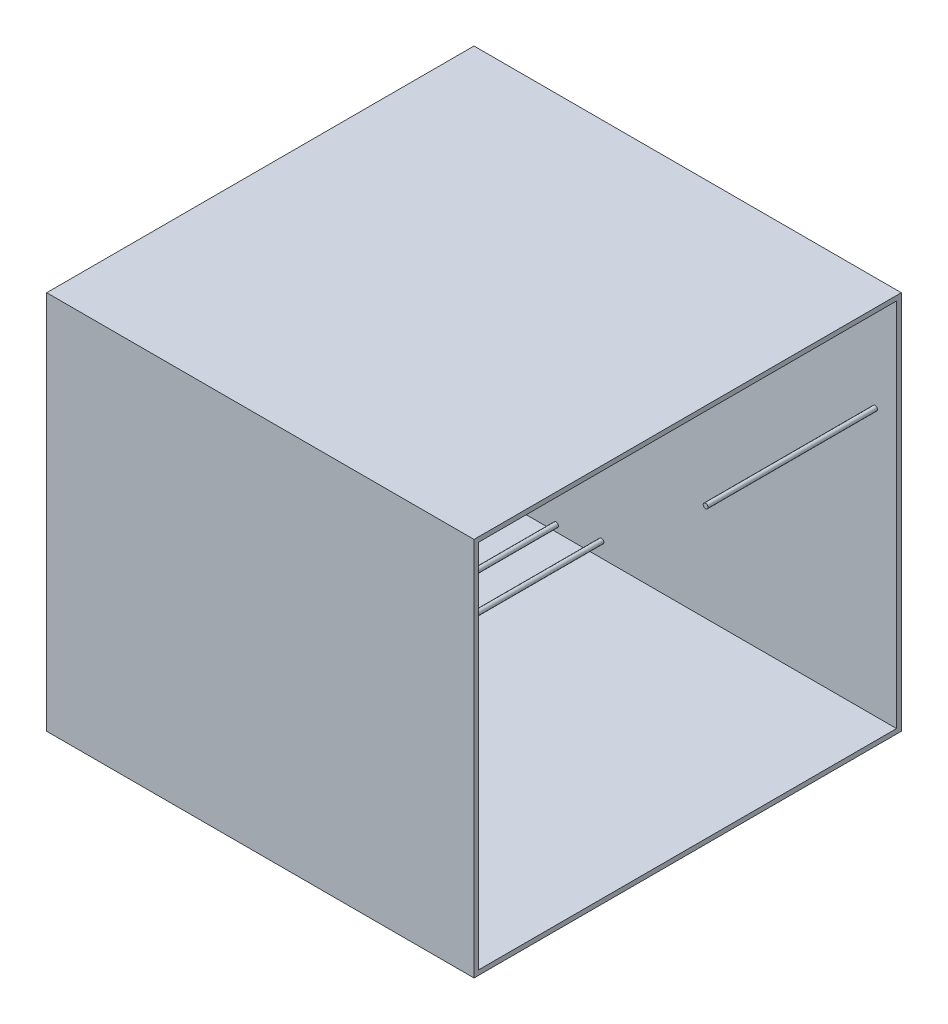
SolidWorks part; units mm, degrees
ref_plane "Plano frontal" through (0, 0, 0) normal (0, 0, 1) x (1, 0, 0)
ref_plane "Plano superior" through (0, 0, 0) normal (0, 1, 0) x (1, 0, 0)
ref_plane "Plano direito" through (0, 0, 0) normal (1, 0, 0) x (0, 0, -1)
sketch "Esboço1" plane through (0, 0, 0) normal (1, 0, 0) x (0, 0, -1)
  line L1 (0, 0) -> (450, 0)
  line L2 (0, 0) -> (0, 400)
  line L3 (0, 400) -> (450, 400)
  line L4 (450, 0) -> (450, 400)
  line L5 (5, 5) -> (445, 5)
  line L6 (5, 5) -> (5, 395)
  line L7 (5, 395) -> (445, 395)
  line L8 (445, 5) -> (445, 395)
  line L9 (5, 5) -> (445, 395) construction
  line L10 (5, 395) -> (445, 5) construction
  point P5 (225, 200)
  dimension "D1" = 450
  dimension "D2" = 400
  dimension "D3" = 5
  dimension "D4" = 5
  dimension "D5" = 5
  dimension "D6" = 5
extrude "Ressalto-extrusão1" add sketch "Esboço1" along normal blind 450
sketch "Esboço2" plane through (0, 0, 0) normal (0, 0, 1) x (1, 0, 0)
  line L0 (0, 199.95) -> (150.03, 199.95) construction
  line L1 (0, 400) -> (0, 0) construction
  line L2 (150.03, 199.95) -> (150.03, 0) construction
  line L3 (450, 0) -> (0, 0) construction
  line L4 (0, 268.16) -> (347.87, 268.16) construction
  line L5 (347.87, 268.16) -> (347.87, 0) construction
  line L6 (0, 282.17) -> (400.68, 282.17) construction
  line L7 (400.68, 282.17) -> (400.68, 0) construction
  line L9 (450, 400) -> (450, 0) construction
  circle A0 centre (150.03, 199.95) radius 7.5
  circle A1 centre (347.87, 268.16) radius 2.5
  circle A2 centre (400.68, 282.17) radius 2.5
  dimension "D7" = 49.32
  dimension "D1" = 150.03
  dimension "D2" = 199.95
  dimension "D3" = 347.87
  dimension "D4" = 268.16
  dimension "D5" = 400.68
  dimension "D6" = 282.17
  dimension "D8" = 102.13
extrude "Ressalto-extrusão2" add sketch "Esboço2" against normal blind 183.55 contours A2 region at (400.68, 282.17, 0)
extrude "Ressalto-extrusão3" add sketch "Esboço2<3>" against normal blind 188.55 contours A1
sketch "Esboço2<3>" plane through (0, 0, 0) normal (0, 0, 1) x (1, 0, 0) same geometry as "Esboço2"
extrude "Ressalto-extrusão4" add sketch "Esboço2<4>" against normal blind 181.55 contours A0
sketch "Esboço2<4>" plane through (0, 0, 0) normal (0, 0, 1) x (1, 0, 0) same geometry as "Esboço2"
sketch "Esboço3" plane through (0, 0, -450) normal (0, 0, -1) x (-1, 0, 0)
  line L0 (0, 348.09) -> (-353.49, 348.09) construction
  line L1 (0, 0) -> (0, 400) construction
  line L2 (-353.49, 348.09) -> (-353.49, 0) construction
  line L3 (-450, 0) -> (0, 0) construction
  line L4 (0, 199.95) -> (-150.03, 199.95) construction
  line L5 (-150.03, 199.95) -> (-150.03, 0) construction
  line L6 (0, 285.92) -> (-427.35, 285.92) construction
  line L7 (-427.35, 285.92) -> (-427.35, 0) construction
  circle A0 centre (-150.03, 199.95) radius 7.5
  circle A1 centre (-353.49, 348.09) radius 2.5
  circle A2 centre (-427.35, 285.92) radius 2.5
  dimension "D1" = 353.49
  dimension "D2" = 348.09
  dimension "D3" = 427.35
  dimension "D4" = 285.92
extrude "Ressalto-extrusão5" add sketch "Esboço3" against normal blind 183.45 contours A2
extrude "Ressalto-extrusão6" add sketch "Esboço3<3>" against normal blind 183.45 contours A1
sketch "Esboço3<3>" plane through (0, 0, -450) normal (0, 0, -1) x (-1, 0, 0) same geometry as "Esboço3"
extrude "Ressalto-extrusão7" add sketch "Esboço3<4>" against normal blind 120.45 contours A0
sketch "Esboço3<4>" plane through (0, 0, -450) normal (0, 0, -1) x (-1, 0, 0) same geometry as "Esboço3"
